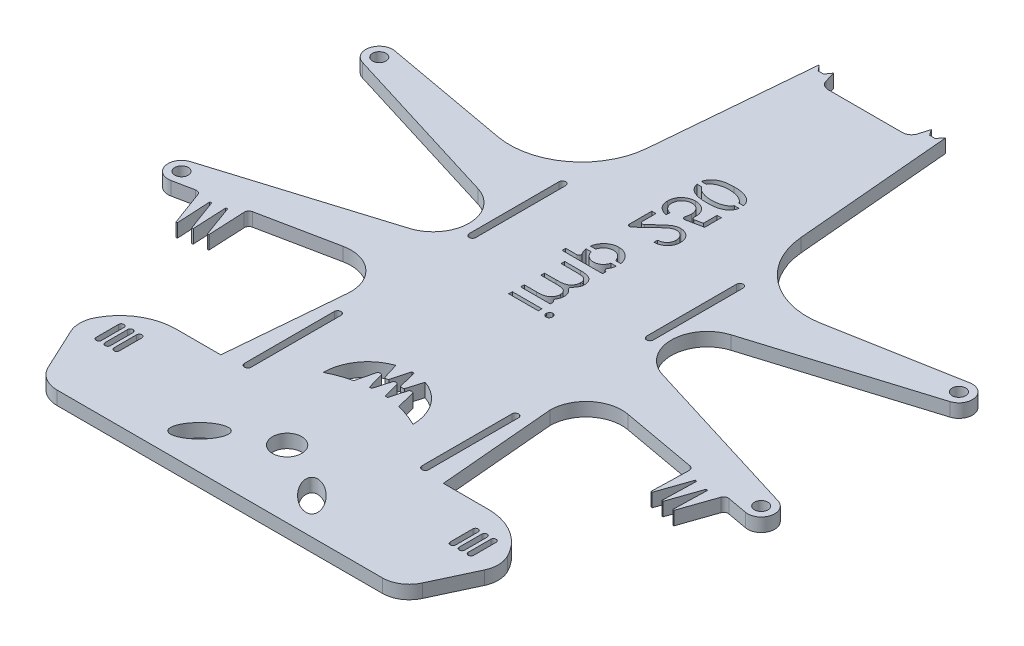
SolidWorks part; units mm, degrees
ref_plane "前视基准面" through (0, 0, 0) normal (0, 0, 1) x (1, 0, 0)
ref_plane "上视基准面" through (0, 0, 0) normal (0, 1, 0) x (1, 0, 0)
ref_plane "右视基准面" through (0, 0, 0) normal (1, 0, 0) x (0, 0, -1)
sketch "草图1" plane through (0, 0, 0) normal (0, 1, 0) x (1, 0, 0)
  line L5 (-65.3843, -19.1333) -> (-28.1418, -7.6445)
  line L6 (-63.9021, -24.9398) -> (-58.5124, -23.8437)
  line L8 (0, 0) -> (0, 91.5573) construction
  line L9 (0, 0) -> (-115.8836, 0) construction
  line L15 (0, 0) -> (0, -124.2991) construction
  line L16 (-15, -65) -> (15, -65) construction
  line L20 (-15.42, -115) -> (17.43, -115) construction
  line L21 (-28, -109.5) -> (-28, -90)
  line L22 (28, -109.5) -> (28, -90)
  line L23 (-17.5, -120) -> (17.5, -120)
  line L28 (22.5, -27) -> (22.5, 27) construction
  line L29 (-22.5, -27) -> (-22.5, 27) construction
  line L30 (28.1418, -7.6445) -> (65.3843, -19.1333)
  line L31 (28.1418, 7.6445) -> (65.3843, 19.1333)
  line L32 (-28, -90) -> (28, -90) construction
  line L33 (28, -90) -> (22.5, -27)
  line L34 (-28, -90) -> (-22.5, -27)
  line L35 (63.9635, -24.9516) -> (58.59, -23.9749)
  line L36 (0, 0) -> (104.501, 0) construction
  line L37 (-28.1418, 7.6445) -> (-65.3843, 19.1333)
  line L39 (22.5, 70) -> (22.5, 27) construction
  line L40 (-22.5, 70) -> (-22.5, 27) construction
  line L41 (31.9307, 19.129) -> (63.9635, 24.9516) construction
  line L42 (-63.9635, 24.9516) -> (-31.9307, 19.129) construction
  line L43 (-17.1562, 34.2114) -> (-14.0779, 69.4717)
  line L44 (63.9635, 24.9516) -> (35.957, 19.8608)
  line L45 (-63.9635, 24.9516) -> (-35.957, 19.8608)
  line L46 (17.1562, 34.2114) -> (14.0779, 69.4717)
  line L47 (51.4721, -37.7563) -> (54.614, -20.4713) construction
  line L48 (43.8592, -31.4611) -> (59.0133, -34.2157) construction
  line L49 (52.3717, -31.9686) -> (52.5699, -24.4476)
  line L50 (52.6668, -32.0223) -> (55.128, -24.9126)
  line L51 (-51.727, -34.6283) -> (-54.8464, -19.2902) construction
  line L52 (-52.1667, -31.7138) -> (-52.5215, -24.1986)
  line L53 (-52.4606, -31.7736) -> (-55.0694, -24.7168)
  line L54 (-55.4614, -24.7965) -> (-55.0688, -32.3041)
  line L55 (-55.3628, -32.3639) -> (-58.5124, -23.8437)
  line L56 (-52.1296, -24.1189) -> (-49.5585, -31.1834)
  line L57 (-49.2645, -31.1236) -> (-49.693, -22.05)
  line L58 (-55.3108, -33.3973) -> (-45.8391, -31.4709) construction
  line L59 (-49.693, -22.05) -> (-32.0641, -18.4647)
  line L60 (49.42, -31.4321) -> (49.6594, -22.3516)
  line L61 (49.7152, -31.4858) -> (52.1764, -24.3761)
  line L62 (55.3233, -32.5052) -> (55.5216, -24.9841)
  line L63 (55.6185, -32.5588) -> (58.59, -23.9749)
  line L64 (49.6594, -22.3516) -> (31.9307, -19.129)
  line L65 (-14.4088, 65.6811) -> (14.4088, 65.6811) construction
  line L70 (-10.8845, 69.4717) -> (-10.1819, 67.1107)
  line L75 (10.8788, 69.4717) -> (10.1832, 67.115)
  line L76 (-8.265, 65.6811) -> (8.265, 65.6811)
  line L77 (-58.5124, -23.8437) -> (-49.693, -22.05) construction
  line L78 (-55.0119, -33.3365) -> (-57.0048, -23.5371) construction
  line L79 (-49.2076, -32.156) -> (-51.2006, -22.3566) construction
  line L80 (-55.3108, -31.8666) -> (-48.2781, -30.4363) construction
  line L81 (-55.5726, -23.2458) -> (-53.8786, -31.5753) construction
  line L82 (-52.6328, -22.6479) -> (-50.9388, -30.9774) construction
  line L83 (-55.174, -25.2057) -> (-50.3177, -24.218) construction
  line L84 (49.6594, -22.3516) -> (58.59, -23.9749) construction
  line L85 (49.3846, -32.4655) -> (51.1731, -22.6267) construction
  line L86 (55.2879, -33.5385) -> (57.0763, -23.6997) construction
  line L87 (49.6529, -30.9897) -> (55.5562, -32.0627) construction
  line L88 (52.6489, -22.895) -> (50.8605, -32.7337) construction
  line L89 (55.6005, -23.4315) -> (53.8121, -33.2703) construction
  line L90 (52.2912, -24.8627) -> (55.2428, -25.3992) construction
  line L95 (-13, 68.1811) -> (-11.8, 68.1811)
  line L96 (13, 68.1811) -> (14.0779, 69.4717)
  line L97 (-13, 68.1811) -> (-14.0779, 69.4717)
  line L98 (-10.8845, 69.4717) -> (-11.8, 68.1811)
  line L99 (10.8788, 69.4717) -> (11.8, 68.1811)
  line L100 (11.8, 68.1811) -> (13, 68.1811)
  circle A0 centre (-64.5, 30) radius 1.5 construction
  circle A1 centre (64.5, 30) radius 1.5 construction
  circle A2 centre (64.5, -30) radius 1.5 construction
  circle A3 centre (-64.5, -30) radius 1.5 construction
  circle A4 centre (-64.5, 30) radius 3 construction
  circle A5 centre (64.5, 30) radius 3 construction
  circle A6 centre (64.5, -30) radius 3 construction
  circle A7 centre (-64.5, -30) radius 3 construction
  circle A10 centre (-64.5, 22) radius 1.5
  circle A11 centre (64.5, 22) radius 1.5
  circle A12 centre (64.5, -22) radius 1.5
  circle A13 centre (-64.5, -22) radius 1.5
  circle A22 centre (0, -90) radius 25
  circle A23 centre (-15, -65) radius 1
  circle A24 centre (15, -65) radius 1
  circle A25 centre (-15.42, -115) radius 1
  circle A26 centre (17.43, -115) radius 1
  arc A27 (-17.5, -120) -> (-28, -109.5) centre (-17.5, -109.5) cw
  arc A28 (17.5, -120) -> (28, -109.5) centre (17.5, -109.5) ccw
  arc A42 (63.9635, -24.9516) -> (65.3843, -19.1333) centre (64.5, -22) ccw
  arc A43 (65.3843, 19.1333) -> (63.9635, 24.9516) centre (64.5, 22) ccw
  arc A44 (28.1418, -7.6445) -> (28.1418, 7.6445) centre (30.5, 0) cw
  arc A46 (22.5, -27) -> (31.9307, -19.129) centre (30.5, -27) cw
  arc A47 (-65.3843, -19.1333) -> (-63.9021, -24.9398) centre (-64.5, -22) ccw
  arc A49 (-28.1418, -7.6445) -> (-28.1418, 7.6445) centre (-30.5, 0) ccw
  arc A50 (-22.5, -27) -> (-32.0641, -18.4647) centre (-30.4697, -26.3042) ccw
  arc A51 (-63.9635, 24.9516) -> (-65.3843, 19.1333) centre (-64.5, 22) ccw
  arc A52 (31.9307, 19.129) -> (22.5, 27) centre (30.5, 27) cw construction
  arc A53 (-31.9307, 19.129) -> (-22.5, 27) centre (-30.5, 27) ccw construction
  arc A54 (-35.957, 19.8608) -> (-17.1562, 34.2114) centre (-33.0955, 35.6029) ccw
  arc A55 (17.1562, 34.2114) -> (35.957, 19.8608) centre (33.0955, 35.6029) ccw
  arc A56 (-8.265, 65.6811) -> (-10.1819, 67.1107) centre (-8.265, 67.6811) cw
  arc A57 (10.1832, 67.115) -> (8.265, 65.6811) centre (8.265, 67.6811) cw
  arc A58 (-55.3628, -32.3639) -> (-55.0688, -32.3041) centre (-55.3108, -31.8666) ccw
  arc A59 (-52.4606, -31.7736) -> (-52.1667, -31.7138) centre (-52.4087, -31.2763) ccw
  arc A60 (-49.5585, -31.1834) -> (-49.2645, -31.1236) centre (-49.5066, -30.6861) ccw
  arc A61 (-55.4614, -24.7965) -> (-55.0694, -24.7168) centre (-55.174, -25.2057) cw
  arc A62 (-52.5215, -24.1986) -> (-52.1296, -24.1189) centre (-52.2342, -24.6078) cw
  arc A63 (49.42, -31.4321) -> (49.7152, -31.4858) centre (49.6529, -30.9897) ccw
  arc A64 (52.3717, -31.9686) -> (52.6668, -32.0223) centre (52.6045, -31.5262) ccw
  arc A65 (55.3233, -32.5052) -> (55.6185, -32.5588) centre (55.5562, -32.0627) ccw
  arc A66 (52.1764, -24.3761) -> (52.5699, -24.4476) centre (52.2912, -24.8627) cw
  arc A67 (55.128, -24.9126) -> (55.5216, -24.9841) centre (55.2428, -25.3992) cw
  point P0 (0, 0)
  point P109 (-9.7565, 65.6811)
  point P112 (9.76, 65.6811)
  dimension "D1" = 3
  dimension "D6" = 6
  dimension "D7" = 6
  dimension "D8" = 6
  dimension "D9" = 6
  dimension "D15" = 3
  dimension "D18" = 6
  dimension "D19" = 16
  dimension "D20" = 8
  dimension "D21" = 22
  dimension "D22" = 50
  dimension "D28" = 2
  dimension "D31" = 2
  dimension "D25" = 45
  dimension "D37" = 27
  dimension "D38" = 16
  dimension "D39" = 10
  dimension "D40" = 6
  dimension "D41" = 6
  dimension "D44" = 8
  dimension "D45" = 8
  dimension "D27" = 22.5
  dimension "D47" = 10.5
  dimension "D48" = 10
  dimension "D17" = 8
  dimension "D12" = 6
  dimension "D13" = 8
  dimension "D16" = 8
  dimension "D60" = 2
  dimension "D61" = 2
  dimension "D62" = 0.5
  dimension "D67" = 0.5
  dimension "D70" = 0.5
  dimension "D74" = 0.5
  dimension "D77" = 0.5
  dimension "D81" = 0.5
  dimension "D66" = 0.5
  dimension "D86" = 0.5
  dimension "D90" = 0.5
  dimension "D93" = 0.5
  dimension "D2" = 129
  dimension "D3" = 60
  dimension "D4" = 30
  dimension "D5" = 64.5
  dimension "D10" = 27
  dimension "D11" = 27
  dimension "D14" = 9.7565
  dimension "D23" = 30
  dimension "D24" = 15
  dimension "D26" = 30
  dimension "D29" = 32.85
  dimension "D30" = 2.43
  dimension "D32" = 27
  dimension "D33" = 28
  dimension "D34" = 28
  dimension "D35" = 35
  dimension "D36" = 17.5
  dimension "D42" = 45
  dimension "D43" = 22.5
  dimension "D46" = 120
  dimension "D49" = 10
  dimension "D50" = 3
  dimension "D51" = 3
  dimension "D52" = 3
  dimension "D53" = 1.5
  dimension "D54" = 10
  dimension "D55" = 3
  dimension "D56" = 1.5
  dimension "D57" = 65.6811
  dimension "D58" = 10.1819
  dimension "D59" = 10.1832
  dimension "D63" = 1.5
  dimension "D64" = 0.15
  dimension "D65" = 0.15
  dimension "D68" = 0.15
  dimension "D69" = 0.15
  dimension "D71" = 0.15
  dimension "D72" = 0.15
  dimension "D73" = 2
  dimension "D75" = 0.2
  dimension "D76" = 0.2
  dimension "D78" = 0.2
  dimension "D79" = 0.2
  dimension "D80" = 1.5
  dimension "D82" = 0.15
  dimension "D83" = 0.15
  dimension "D84" = 0.15
  dimension "D85" = 0.15
  dimension "D87" = 0.15
  dimension "D88" = 0.15
  dimension "D89" = 2
  dimension "D91" = 0.2
  dimension "D92" = 0.2
  dimension "D94" = 0.2
  dimension "D95" = 0.2
  dimension "D96" = 3.7906
  dimension "D97" = 8.265
  dimension "D98" = 3.7906
  dimension "D99" = 8.265
  dimension "D100" = 9.76
  dimension "D101" = 22.5
  dimension "D102" = 26
  dimension "D103" = 13
  dimension "D104" = 2.5
  dimension "D105" = 10.8845
  dimension "D106" = 10.8788
  dimension "D107" = 1.2
  dimension "D108" = 1.2
extrude "凸台-拉伸1" add sketch "草图1" along normal blind 3
sketch "草图2" plane through (0, 0, 0) normal (0, -1, 0) x (1, 0, 0)
  line L0 (0, 133.3282) -> (0, -97.043) construction
  line L1 (-19.75, 2) -> (-19.75, -18) construction
  line L2 (-19, 2) -> (-19, -18)
  line L3 (-20.5, 2) -> (-20.5, -18)
  line L4 (19.75, 2) -> (19.75, -18) construction
  line L5 (20.5, 2) -> (20.5, -18)
  line L6 (19, 2) -> (19, -18)
  line L7 (0, 0) -> (56.7659, 0) construction
  line L8 (-19.75, 52) -> (-19.75, 32) construction
  line L9 (-19, 52) -> (-19, 32)
  line L10 (-20.5, 52) -> (-20.5, 32)
  line L11 (19.75, 52) -> (19.75, 32) construction
  line L12 (20.5, 52) -> (20.5, 32)
  line L13 (19, 52) -> (19, 32)
  arc A0 (-19, 2) -> (-20.5, 2) centre (-19.75, 2) ccw
  arc A1 (-20.5, -18) -> (-19, -18) centre (-19.75, -18) ccw
  arc A2 (20.5, 2) -> (19, 2) centre (19.75, 2) ccw
  arc A3 (19, -18) -> (20.5, -18) centre (19.75, -18) ccw
  arc A4 (-19, 52) -> (-20.5, 52) centre (-19.75, 52) ccw
  arc A5 (-20.5, 32) -> (-19, 32) centre (-19.75, 32) ccw
  arc A6 (20.5, 52) -> (19, 52) centre (19.75, 52) ccw
  arc A7 (19, 32) -> (20.5, 32) centre (19.75, 32) ccw
  arc A8 (-10, 45) -> (10, 45) centre (0, 45) ccw
  arc A9 (-10, 45) -> (10, 45) centre (0, 64.5959) ccw
  point P5 (-19.75, -8)
  point P10 (19.75, -8)
  point P19 (-19.75, 42)
  point P26 (19.75, 42)
  dimension "D6" = 42
  dimension "D8" = 10
  dimension "D9" = 22
  dimension "D1" = 1.5
  dimension "D2" = 20
  dimension "D3" = 19
  dimension "D4" = 19
  dimension "D5" = 8
  dimension "D7" = 45
  dimension "D10" = 10
extrude "切除-拉伸1" cut sketch "草图2" against normal blind 3
sketch "草图3" plane through (0, 0, 0) normal (0, -1, 0) x (1, 0, 0)
  line L0 (0, 67.5428) -> (0, 43.0807) construction
  line L1 (-3.5, 60.2388) -> (-3.5, 43.3854) construction
  line L2 (3.5, 60.0167) -> (3.5, 43.3854) construction
  line L3 (-1.5, 42.6471) -> (-0.4454, 38.96)
  line L4 (0.4454, 38.96) -> (1.5, 42.6471)
  line L5 (-5.2946, 37.5) -> (4.5072, 37.5) construction
  line L6 (-3.0546, 38.96) -> (-2, 42.687)
  line L7 (-5, 43.1716) -> (-3.9454, 38.96)
  line L8 (3.0546, 38.96) -> (2, 42.687)
  line L9 (3.9454, 38.96) -> (5, 43.1716)
  line L10 (-5.8174, 40.5) -> (6.3675, 40.5) construction
  line L11 (-5.8021, 35) -> (6.2608, 35) construction
  line L12 (-1.75, 52.0659) -> (-1.75, 44.2103) construction
  line L13 (1.75, 52.0659) -> (1.75, 33.5429) construction
  line L14 (-1.3046, 39.04) -> (-0.25, 35.0031)
  line L15 (-2.1906, 39.0439) -> (-3.25, 35.5429)
  line L16 (1.3046, 39.04) -> (0.25, 35.0031)
  line L17 (2.1954, 39.04) -> (3.25, 35.5429)
  line L18 (-5, 43.1716) -> (-5, 44.1716)
  line L19 (-5, 44.1716) -> (5, 44.1716)
  line L20 (5, 44.1716) -> (5, 43.1716)
  line L21 (-2, 42.687) -> (-2, 43.687)
  line L22 (-2, 43.687) -> (-1.5, 43.687)
  line L23 (-1.5, 43.687) -> (-1.5, 42.6471)
  line L24 (1.5, 42.6471) -> (1.5, 43.687)
  line L25 (1.5, 43.687) -> (2, 43.687)
  line L26 (2, 43.687) -> (2, 42.687)
  line L27 (-3.25, 35.5429) -> (-3.25, 33.5429)
  line L28 (-3.25, 33.5429) -> (3.25, 33.5429)
  line L29 (3.25, 33.5429) -> (3.25, 35.5429)
  line L30 (-0.25, 35.0031) -> (-0.25, 34.0031)
  line L31 (-0.25, 34.0031) -> (0.25, 34.0031)
  line L32 (0.25, 34.0031) -> (0.25, 35.0031)
  arc A0 (-10, 45) -> (10, 45) centre (0, 64.5959) ccw construction
  arc A1 (-10, 45) -> (10, 45) centre (0, 64.5959) ccw construction
  arc A2 (-10, 45) -> (10, 45) centre (0, 45) ccw construction
  arc A3 (-10, 45) -> (10, 45) centre (0, 45) ccw construction
  arc A4 (-3.9454, 38.96) -> (-3.0546, 38.96) centre (-3.5, 39.5) ccw
  arc A5 (0.4454, 38.96) -> (-0.4454, 38.96) centre (0, 39.5) cw
  arc A6 (3.9454, 38.96) -> (3.0546, 38.96) centre (3.5, 39.5) cw
  arc A7 (-2.1906, 39.0439) -> (-1.3046, 39.04) centre (-1.75, 38.5) cw
  arc A8 (1.3046, 39.04) -> (2.1954, 39.04) centre (1.75, 38.5) cw
  dimension "D21" = 0.7
  dimension "D25" = 0.7
  dimension "D26" = 0.7
  dimension "D28" = 0.7
  dimension "D33" = 0.7
  dimension "D1" = 3.5
  dimension "D2" = 3.5
  dimension "D3" = 7.5
  dimension "D4" = 3
  dimension "D5" = 1.5
  dimension "D6" = 1.5
  dimension "D7" = 1.5
  dimension "D8" = 3
  dimension "D9" = 1.5
  dimension "D10" = 5.5
  dimension "D11" = 1.75
  dimension "D12" = 3.5
  dimension "D13" = 1.5
  dimension "D14" = 1.5
  dimension "D15" = 1.5
  dimension "D16" = 1.5
  dimension "D17" = 1
  dimension "D18" = 1
  dimension "D19" = 1
  dimension "D20" = 2
  dimension "D22" = 2
  dimension "D23" = 1.46
  dimension "D24" = 1.46
  dimension "D27" = 2
  dimension "D29" = 1.4561
  dimension "D30" = 1.46
  dimension "D31" = 2
  dimension "D32" = 1.46
  dimension "D34" = 1.46
extrude "凸台-拉伸2" add sketch "草图3" against normal blind 3
sketch "草图4" plane through (0, 0, 0) normal (0, -1, 0) x (1, 0, 0)
  line L0 (0, 0) -> (0, 140.5969) construction
  line L1 (-28, 108) -> (-21.4476, 108)
  line L2 (-17.5, 120) -> (17.5, 120) construction
  line L3 (-28, 90) -> (28, 90) construction
  line L4 (-28, 90) -> (-28, 109.5) construction
  line L5 (28, 109.5) -> (28, 90) construction
  line L6 (-21.4476, 113) -> (-21.4476, 119.2297)
  line L7 (21.4476, 119.2297) -> (21.4476, 113)
  line L8 (21.4476, 108) -> (28, 108)
  line L9 (-21.4476, 113) -> (-27.3995, 113)
  line L10 (21.4476, 113) -> (27.3995, 113)
  line L11 (-28, 108) -> (-28, 90)
  line L12 (28, 108) -> (28, 90)
  circle A0 centre (0, 90) radius 25 construction
  circle A1 centre (0, 90) radius 25 construction
  arc A2 (-21.4476, 108) -> (-28, 90) centre (0, 90) ccw
  arc A3 (28, 90) -> (21.4476, 108) centre (0, 90) ccw
  arc A4 (-17.5, 120) -> (-28, 109.5) centre (-17.5, 109.5) ccw construction
  arc A5 (28, 109.5) -> (17.5, 120) centre (17.5, 109.5) ccw construction
  arc A6 (-21.4476, 119.2297) -> (-27.3995, 113) centre (-17.5, 109.5) ccw
  arc A7 (27.3995, 113) -> (21.4476, 119.2297) centre (17.5, 109.5) ccw
  dimension "D1" = 12
  dimension "D4" = 5
  dimension "D5" = 5
extrude "切除-拉伸2" cut sketch "草图4" against normal blind 3
sketch "草图6" plane through (0, 0, 0) normal (0, -1, 0) x (1, 0, 0)
  line L0 (-21.4476, 119.2297) -> (-21.4476, 139)
  line L1 (-18.4476, 142) -> (18.4476, 142)
  line L2 (21.4476, 139) -> (21.4476, 119.2297)
  line L3 (-17.5, 120) -> (17.5, 120) construction
  line L4 (0, 0) -> (0, 166.5632) construction
  line L5 (-21.4476, 131) -> (21.4476, 131) construction
  line L6 (-21.4476, 139) -> (-18.4476, 142)
  line L7 (18.4476, 142) -> (21.4476, 139)
  line L8 (-21.4476, 119.2297) -> (21.4476, 119.2297)
  circle A0 centre (0, 131) radius 3
  point P1 (-21.4476, 142)
  point P4 (21.4476, 142)
  dimension "D3" = 6
  dimension "D1" = 22
  dimension "D2" = 11
extrude "凸台-拉伸3" add sketch "草图6" against normal blind 3
sketch "草图7" plane through (0, 0, 0) normal (0, -1, 0) x (1, 0, 0)
  line L0 (-21.4476, 108) -> (-28, 108) construction
  line L1 (-21.4476, 108) -> (-28, 108) construction
  line L2 (28, 108) -> (21.4476, 108) construction
  line L3 (28, 108) -> (21.4476, 108) construction
  line L4 (-22.5, 27) -> (-28, 90) construction
  line L5 (-26.6119, 74.1001) -> (-28, 90)
  line L6 (28, 90) -> (22.5, 27) construction
  line L7 (28, 90) -> (26.6119, 74.1001)
  line L8 (-25.2389, 108) -> (-21.4476, 108)
  line L9 (21.4476, 108) -> (25.2389, 108)
  circle A0 centre (0, 90) radius 25 construction
  circle A1 centre (0, 90) radius 25 construction
  arc A2 (-25.2389, 108) -> (-26.6119, 74.1001) centre (0, 90) ccw
  arc A3 (26.6119, 74.1001) -> (25.2389, 108) centre (0, 90) ccw
  arc A4 (-21.4476, 108) -> (-28, 90) centre (0, 90) ccw construction
  arc A5 (-21.4476, 108) -> (-28, 90) centre (0, 90) ccw
  arc A6 (28, 90) -> (21.4476, 108) centre (0, 90) ccw construction
  arc A7 (28, 90) -> (21.4476, 108) centre (0, 90) ccw
  dimension "D1" = 62
extrude "凸台-拉伸4" add sketch "草图7" against normal blind 3
sketch "草图8" plane through (0, 0, 0) normal (0, -1, 0) x (1, 0, 0)
  line L0 (-22.5, 27) -> (-26.6119, 74.1001) construction
  line L1 (-25.6429, 63) -> (-26.6119, 74.1001)
  line L2 (26.6119, 74.1001) -> (22.5, 27) construction
  line L3 (26.6119, 74.1001) -> (25.6429, 63)
  line L4 (-25.6429, 63) -> (25.6429, 63)
  line L5 (-25.2389, 108) -> (-28, 108) construction
  line L6 (-25.2389, 108) -> (-28, 108)
  line L7 (-28, 108) -> (-28, 109.5) construction
  line L8 (-28, 108) -> (-28, 109.5)
  line L9 (28, 108) -> (25.2389, 108) construction
  line L10 (28, 109.5) -> (28, 108) construction
  line L11 (21.4476, 113) -> (27.3995, 113) construction
  line L12 (21.4476, 139) -> (21.4476, 113) construction
  line L13 (21.4476, 139) -> (18.4476, 142) construction
  line L14 (18.4476, 142) -> (-18.4476, 142) construction
  line L15 (-18.4476, 142) -> (-21.4476, 139) construction
  line L16 (-21.4476, 113) -> (-21.4476, 139) construction
  line L17 (-27.3995, 113) -> (-21.4476, 113) construction
  line L18 (28, 108) -> (25.2389, 108)
  line L19 (28, 109.5) -> (28, 108)
  line L20 (21.4476, 113) -> (27.3995, 113)
  line L21 (21.4476, 139) -> (21.4476, 113)
  line L22 (21.4476, 139) -> (18.4476, 142)
  line L23 (18.4476, 142) -> (-18.4476, 142)
  line L24 (-18.4476, 142) -> (-21.4476, 139)
  line L25 (-21.4476, 113) -> (-21.4476, 139)
  line L26 (-27.3995, 113) -> (-21.4476, 113)
  circle A1 centre (0, 63) radius 3.25 construction
  arc A2 (-25.2389, 108) -> (-26.6119, 74.1001) centre (0, 90) ccw construction
  arc A3 (-25.2389, 108) -> (-26.6119, 74.1001) centre (0, 90) ccw
  arc A4 (-27.3995, 113) -> (-28, 109.5) centre (-17.5, 109.5) ccw construction
  arc A5 (-27.3995, 113) -> (-28, 109.5) centre (-17.5, 109.5) ccw
  arc A6 (26.6119, 74.1001) -> (25.2389, 108) centre (0, 90) ccw construction
  arc A7 (28, 109.5) -> (27.3995, 113) centre (17.5, 109.5) ccw construction
  arc A8 (26.6119, 74.1001) -> (25.2389, 108) centre (0, 90) ccw
  arc A9 (28, 109.5) -> (27.3995, 113) centre (17.5, 109.5) ccw
  dimension "D1" = 6.5
  dimension "D2" = 63
extrude "切除-拉伸3" cut sketch "草图8" against normal blind 10
sketch "草图10" plane through (0, 0, 0) normal (0, -1, 0) x (1, 0, 0)
  line L0 (-25.6429, 63) -> (25.6429, 63) construction
  line L1 (-46.9976, 63) -> (47.0024, 63) construction
  line L2 (-36.1783, 78) -> (36.1794, 78)
  line L3 (0, 63) -> (0, 109.6816) construction
  line L4 (-34.7501, 53) -> (34.755, 53)
  line L5 (-41.6157, 74.5366) -> (-46.0027, 65.1325)
  line L6 (41.6161, 74.538) -> (46.0066, 65.1333)
  circle A0 centre (0, 63) radius 3.25
  arc A1 (-45.9332, 59.9152) -> (-34.7501, 53) centre (-34.7501, 65.5) ccw
  arc A2 (45.9374, 59.9139) -> (34.755, 53) centre (34.755, 65.5) cw
  arc A3 (-41.6157, 74.5366) -> (-36.1783, 78) centre (-36.1783, 72) cw
  arc A4 (41.6161, 74.538) -> (36.1794, 78) centre (36.1794, 72) ccw
  arc A5 (-45.9332, 59.9152) -> (-46.0027, 65.1325) centre (-40.5653, 62.5959) cw
  arc A6 (45.9374, 59.9139) -> (46.0066, 65.1333) centre (40.5698, 62.5952) ccw
  point P13 (0, 0)
  point P18 (-40, 78)
  point P21 (40, 78)
  point P27 (47.0024, 63)
  dimension "D1" = 6.5
  dimension "D8" = 6
  dimension "D3" = 34.755
  dimension "D9" = 6
  dimension "D10" = 6
  dimension "D11" = 6
  dimension "D2" = 94
  dimension "D4" = 15
  dimension "D5" = 80
  dimension "D6" = 40
  dimension "D7" = 10
  dimension "D12" = 34.7501
extrude "凸台-拉伸5" add sketch "草图10" against normal blind 3
sketch "草图12" plane through (0, 0, 0) normal (0, -1, 0) x (1, 0, 0)
  line L0 (0, 0) -> (0, 80.2882) construction
  line L1 (-24.7698, 53) -> (24.7698, 53) construction
  line L2 (-12.5, 53) -> (-12.5, 78) construction
  line L3 (36.1794, 78) -> (-36.1783, 78) construction
  line L4 (12.5, 53) -> (12.5, 78) construction
  line L5 (-46.412, 70) -> (46.4169, 70) construction
  line L6 (-16.0355, 73.5355) -> (-8.9645, 66.4645) construction
  line L7 (-14.091, 68.409) -> (-10.909, 71.591) construction
  line L8 (-41.412, 63.5) -> (-41.412, 58.5) construction
  line L9 (-40.812, 63.5) -> (-40.812, 58.5)
  line L10 (-42.012, 63.5) -> (-42.012, 58.5)
  line L11 (-46.412, 61) -> (46.4169, 61) construction
  line L12 (-39.412, 63.5) -> (-39.412, 58.5) construction
  line L13 (-38.812, 63.5) -> (-38.812, 58.5)
  line L14 (-40.012, 63.5) -> (-40.012, 58.5)
  line L15 (-37.412, 63.5) -> (-37.412, 58.5) construction
  line L16 (-36.812, 63.5) -> (-36.812, 58.5)
  line L17 (-38.012, 63.5) -> (-38.012, 58.5)
  line L18 (37.412, 63.5) -> (37.412, 58.5) construction
  line L19 (36.812, 63.5) -> (36.812, 58.5)
  line L20 (38.012, 63.5) -> (38.012, 58.5)
  line L21 (39.412, 63.5) -> (39.412, 58.5) construction
  line L22 (38.812, 63.5) -> (38.812, 58.5)
  line L23 (40.012, 63.5) -> (40.012, 58.5)
  line L24 (41.412, 63.5) -> (41.412, 58.5) construction
  line L25 (40.812, 63.5) -> (40.812, 58.5)
  line L26 (42.012, 63.5) -> (42.012, 58.5)
  arc A0 (3.25, 63) -> (-3.25, 63) centre (0, 63) ccw construction
  arc A1 (3.25, 63) -> (-3.25, 63) centre (0, 63) ccw construction
  circle A2 centre (0, 63) radius 3.25
  arc A4 (-45.9332, 59.9152) -> (-34.7501, 53) centre (-34.7501, 65.5) ccw construction
  arc A5 (34.755, 53) -> (45.9374, 59.9139) centre (34.755, 65.5) ccw construction
  arc A6 (34.755, 53) -> (45.9374, 59.9139) centre (34.755, 65.5) ccw construction
  arc A7 (-40.812, 63.5) -> (-42.012, 63.5) centre (-41.412, 63.5) ccw
  arc A8 (-42.012, 58.5) -> (-40.812, 58.5) centre (-41.412, 58.5) ccw
  arc A10 (-45.9332, 59.9152) -> (-34.7501, 53) centre (-34.7501, 65.5) ccw construction
  arc A11 (-38.812, 63.5) -> (-40.012, 63.5) centre (-39.412, 63.5) ccw
  arc A12 (-40.012, 58.5) -> (-38.812, 58.5) centre (-39.412, 58.5) ccw
  arc A13 (-36.812, 63.5) -> (-38.012, 63.5) centre (-37.412, 63.5) ccw
  arc A14 (-38.012, 58.5) -> (-36.812, 58.5) centre (-37.412, 58.5) ccw
  arc A15 (36.812, 63.5) -> (38.012, 63.5) centre (37.412, 63.5) cw
  arc A16 (38.012, 58.5) -> (36.812, 58.5) centre (37.412, 58.5) cw
  arc A17 (38.812, 63.5) -> (40.012, 63.5) centre (39.412, 63.5) cw
  arc A18 (40.012, 58.5) -> (38.812, 58.5) centre (39.412, 58.5) cw
  arc A19 (40.812, 63.5) -> (42.012, 63.5) centre (41.412, 63.5) cw
  arc A20 (42.012, 58.5) -> (40.812, 58.5) centre (41.412, 58.5) cw
  ellipse E0 centre (-12.5, 70) end of major axis (-8.9645, 66.4645) minor radius 2.25
  ellipse E1 centre (12.5, 70) end of major axis (8.9645, 66.4645) minor radius 2.25
  point P43 (-41.412, 61)
  point P52 (-39.412, 61)
  point P65 (-37.412, 61)
  point P72 (37.412, 61)
  point P79 (39.412, 61)
  point P86 (41.412, 61)
  dimension "D1" = 24.7698
  dimension "D2" = 12.5
  dimension "D3" = 12.5
  dimension "D4" = 8
  dimension "D5" = 45
  dimension "D6" = 10
  dimension "D7" = 4.5
  dimension "D8" = 8
  dimension "D9" = 1.2
  dimension "D10" = 5
  dimension "D11" = 5
  dimension "D13" = 2
  dimension "D12" = 3
extrude "切除-拉伸4" cut sketch "草图12" against normal blind 3
sketch "草图13" plane through (0, 0, 0) normal (0, -1, 0) x (1, 0, 0)
  line L0 (-4.5, 10) -> (-4.5, -61.1131) construction
  text T0 "imp 250" font "Century Gothic" height 9
  point P0 (-3.4311, 9.1803)
  point P4 (0, -61.9328)
  point P5 (0, 0)
  dimension "D1" = 10
  dimension "D2" = 4.5
extrude "切除-拉伸6" cut sketch "草图13" against normal blind 3
sketch "草图14" plane through (0, 0, 0) normal (0, -1, 0) x (1, 0, 0)
  line L0 (-4.6154, -8.6058) -> (2.1923, -8.5805) construction
  line L1 (-1.1935, -12.0385) -> (-1.1935, -6.2358) construction
  line L2 (0.9803, -8.085) -> (2.4825, -8.085)
  line L3 (0.984, -9.085) -> (2.4825, -9.085)
  line L4 (2.4825, -8.085) -> (2.4825, -9.085)
  line L5 (-4.8695, -8.085) -> (-4.8695, -9.085)
  line L6 (-3.4071, -9.085) -> (-4.8695, -9.085)
  line L7 (-3.4034, -8.085) -> (-4.8695, -8.085)
  line L8 (-0.0036, -30.3846) -> (-0.0036, -36.5) construction
  line L9 (-4.7308, -33.3936) -> (4.7308, -33.3936) construction
  line L10 (3.6134, -32.8936) -> (5.1969, -32.8936)
  line L11 (3.6134, -33.8936) -> (5.1969, -33.8936)
  line L12 (5.1969, -32.8936) -> (5.1969, -33.8936)
  line L13 (-5.2041, -32.8936) -> (-5.2041, -33.8936)
  line L14 (-3.6134, -33.8936) -> (-5.2041, -33.8936)
  line L15 (-3.6134, -32.8936) -> (-5.2041, -32.8936)
  arc A0 (-3.4071, -9.085) -> (0.984, -9.085) centre (-1.2115, -8.5931) ccw
  arc A1 (0.9803, -8.085) -> (-3.4034, -8.085) centre (-1.2115, -8.5931) ccw
  ellipse E0 centre (0, -33.3936) end of major axis (3.7308, -33.3936) minor radius 2.009 (-3.6134, -33.8936) -> (3.6134, -33.8936) ccw
  ellipse E1 centre (0, -33.3936) end of major axis (3.7308, -33.3936) minor radius 2.009 (3.6134, -32.8936) -> (-3.6134, -32.8936) ccw
  spline S0 degree 3 poles (1999.1139, -116.8053) (-26.3066, 9.3137) (3.2455, -0.9377) (2.1371, -9.2675) (2.0596, -9.5946) (1.948, -9.9072) (1.81, -10.2087) (1.6359, -10.4947) (1.4343, -10.7696) (1.2023, -11.0266) (0.9512, -11.264) (0.6812, -11.4693) (0.401, -11.6464) (0.1063, -11.7895) (-0.2005, -11.9017) (-0.5207, -11.9814) (-8.481, -13.118) (-18.5333, 17.21) (115.3668, -2008.5336) knots -4.485893 -4.485893 -4.485893 -4.485893 0.065081 0.128636 0.190653 0.252125 0.313446 0.375227 0.438498 0.503285 0.56801 0.630879 0.692154 0.752552 0.813191 0.873985 0.936258 5.28658 5.28658 5.28658 5.28658 only from (2.1923, -8.5805) to (-1.1935, -12.0385) construction
  spline S1 degree 3 poles (-126.1181, -2007.9855) (16.4205, 17.6121) (6.1423, -13.1304) (-1.8785, -11.9807) (-2.2043, -11.9045) (-2.5148, -11.7904) (-2.8145, -11.6506) (-3.0983, -11.4758) (-3.3689, -11.2706) (-3.6218, -11.0358) (-3.8548, -10.7811) (-4.0584, -10.5088) (-4.2302, -10.2229) (-4.3717, -9.9248) (-4.4807, -9.6135) (-4.5579, -9.2891) (-5.7016, -1.2502) (24.8151, 8.9334) (-2000.9105, -127.4921) knots -4.309051 -4.309051 -4.309051 -4.309051 0.064924 0.12804 0.189582 0.250704 0.311716 0.373236 0.435751 0.500337 0.564943 0.627525 0.689157 0.750169 0.810752 0.872294 0.93541 5.317858 5.317858 5.317858 5.317858 only from (-1.1935, -12.0385) to (-4.6154, -8.6058) construction
  spline S2 degree 3 poles (2.1923, -8.5805) (2.1889, -8.6973) (2.1823, -8.928) (2.1371, -9.2675) (2.0596, -9.5946) (1.948, -9.9072) (1.81, -10.2087) (1.6359, -10.4947) (1.4343, -10.7696) (1.2023, -11.0266) (0.9512, -11.264) (0.6812, -11.4693) (0.401, -11.6464) (0.1063, -11.7895) (-0.2005, -11.9017) (-0.5207, -11.9814) (-0.8531, -12.0289) (-1.0792, -12.0352) (-1.1935, -12.0385) knots 0 0 0 0 0.065081 0.128636 0.190653 0.252125 0.313446 0.375227 0.438498 0.503285 0.56801 0.630879 0.692154 0.752552 0.813191 0.873985 0.936258 1 1 1 1 construction
  spline S3 degree 3 poles (-1.1935, -12.0385) (-1.3103, -12.0353) (-1.5405, -12.0291) (-1.8785, -11.9807) (-2.2043, -11.9045) (-2.5148, -11.7904) (-2.8145, -11.6506) (-3.0983, -11.4758) (-3.3689, -11.2706) (-3.6218, -11.0358) (-3.8548, -10.7811) (-4.0584, -10.5088) (-4.2302, -10.2229) (-4.3717, -9.9248) (-4.4807, -9.6135) (-4.5579, -9.2891) (-4.6059, -8.9516) (-4.6122, -8.7219) (-4.6154, -8.6058) knots 0 0 0 0 0.064924 0.12804 0.189582 0.250704 0.311716 0.373236 0.435751 0.500337 0.564943 0.627525 0.689157 0.750169 0.810752 0.872294 0.93541 1 1 1 1 construction
  spline S4 degree 3 poles (2002.5902, -124.144) (-19.0241, -20.2285) (5.4033, -27.672) (4.703, -33.818) (4.6633, -34.0236) (4.6069, -34.2234) (4.537, -34.4192) (4.4493, -34.6093) (4.3473, -34.795) (4.2274, -34.9733) (4.0937, -35.1461) (3.9426, -35.3092) (3.7756, -35.4627) (3.5945, -35.6085) (3.3957, -35.7423) (3.1829, -35.8698) (2.9521, -35.9839) (2.7074, -36.0938) (2.4418, -36.1886) (2.157, -36.2742) (1.8495, -36.3433) (1.521, -36.4009) (1.1703, -36.4455) (0.798, -36.478) (-12.9041, -37.0747) (-26.9071, -16.0629) (-0.5618, -2036.3224) knots -2.816592 -2.816592 -2.816592 -2.816592 0.033788 0.067194 0.099862 0.132567 0.165151 0.197913 0.231319 0.265083 0.299255 0.334399 0.369943 0.406284 0.444064 0.482998 0.523354 0.565537 0.609613 0.656391 0.705885 0.758325 0.813832 0.872795 0.934722 7.288273 7.288273 7.288273 7.288273 only from (4.7308, -33.3936) to (-0.0036, -36.5) construction
  spline S5 degree 3 poles (6.5367, -2036.3371) (26.9533, -16.2497) (12.9581, -37.0706) (-0.8016, -36.4782) (-1.1719, -36.4447) (-1.5212, -36.4034) (-1.8475, -36.3445) (-2.1539, -36.2776) (-2.4377, -36.1944) (-2.7018, -36.1008) (-2.9454, -35.9933) (-3.1741, -35.8782) (-3.3868, -35.7515) (-3.5856, -35.6169) (-3.7683, -35.4724) (-3.9354, -35.3182) (-4.0869, -35.1543) (-4.2224, -34.9811) (-4.3408, -34.8) (-4.4468, -34.615) (-4.5327, -34.4223) (-4.6053, -34.2261) (-4.6618, -34.0248) (-4.7005, -33.8184) (-5.4503, -28.0104) (20.461, -20.5648) (-2001.5481, -144.3408) knots -6.321684 -6.321684 -6.321684 -6.321684 0.065054 0.126756 0.185491 0.240732 0.29294 0.342141 0.388882 0.432636 0.474483 0.514623 0.553594 0.591409 0.628006 0.663583 0.698759 0.733361 0.767394 0.800969 0.83402 0.866999 0.899733 0.932711 0.96618 3.66314 3.66314 3.66314 3.66314 only from (-0.0036, -36.5) to (-4.7308, -33.3936) construction
  spline S6 degree 3 poles (2.6367, 1969.4415) (-25.8736, -52.8133) (-12.3449, -29.8172) (0.8292, -30.4053) (1.2122, -30.4356) (1.57, -30.4771) (1.9026, -30.5276) (2.2092, -30.595) (2.4912, -30.6717) (2.7495, -30.7605) (2.9876, -30.8608) (3.2098, -30.9699) (3.4159, -31.0922) (3.609, -31.2208) (3.7869, -31.3605) (3.9493, -31.5098) (4.0963, -31.6702) (4.2297, -31.8385) (4.3458, -32.0157) (4.4505, -32.1965) (4.5364, -32.3839) (4.607, -32.5764) (4.6635, -32.7732) (4.7027, -32.9753) (5.4116, -38.9649) (-19.4509, -46.3587) (2002.2715, 64.2043) knots -6.075624 -6.075624 -6.075624 -6.075624 0.068599 0.133255 0.194325 0.251295 0.304533 0.354258 0.400506 0.443439 0.484046 0.523286 0.561079 0.597939 0.633559 0.668551 0.702734 0.736926 0.770536 0.803434 0.836171 0.868452 0.90084 0.933462 0.966255 3.764854 3.764854 3.764854 3.764854 only from (-0.0036, -30.3846) to (4.7308, -33.3936) construction
  spline S7 degree 3 poles (-2002.4555, 60.4569) (19.3725, -46.3462) (-5.4092, -38.9846) (-4.7028, -32.9753) (-4.6631, -32.7735) (-4.6091, -32.577) (-4.5404, -32.3853) (-4.4532, -32.2003) (-4.3519, -32.0196) (-4.2368, -31.844) (-4.1048, -31.6768) (-3.9588, -31.5171) (-3.7952, -31.3689) (-3.6166, -31.231) (-3.4244, -31.1001) (-3.2169, -30.979) (-2.9926, -30.8701) (-2.7532, -30.7676) (-2.493, -30.6772) (-2.2095, -30.598) (-1.9012, -30.532) (-1.5689, -30.4789) (-1.2123, -30.4351) (-0.8309, -30.4055) (12.2073, -29.8149) (25.6301, -52.8613) (-5.415, 1969.409) knots -2.777404 -2.777404 -2.777404 -2.777404 0.033789 0.066626 0.099291 0.131645 0.163602 0.196122 0.228923 0.262181 0.296016 0.330245 0.365089 0.400982 0.437654 0.475743 0.515291 0.556327 0.599681 0.646343 0.696413 0.749766 0.806562 0.867427 0.931883 7.020425 7.020425 7.020425 7.020425 only from (-4.7308, -33.3936) to (-0.0036, -30.3846) construction
  spline S8 degree 3 poles (4.7308, -33.3936) (4.7295, -33.4652) (4.727, -33.6076) (4.703, -33.818) (4.6633, -34.0236) (4.6069, -34.2234) (4.537, -34.4192) (4.4493, -34.6093) (4.3473, -34.795) (4.2274, -34.9733) (4.0937, -35.1461) (3.9426, -35.3092) (3.7756, -35.4627) (3.5945, -35.6085) (3.3957, -35.7423) (3.1829, -35.8698) (2.9521, -35.9839) (2.7074, -36.0938) (2.4418, -36.1886) (2.157, -36.2742) (1.8495, -36.3433) (1.521, -36.4009) (1.1703, -36.4455) (0.798, -36.478) (0.404, -36.4951) (0.1346, -36.4983) (-0.0036, -36.5) knots 0 0 0 0 0.033788 0.067194 0.099862 0.132567 0.165151 0.197913 0.231319 0.265083 0.299255 0.334399 0.369943 0.406284 0.444064 0.482998 0.523354 0.565537 0.609613 0.656391 0.705885 0.758325 0.813832 0.872795 0.934722 1 1 1 1 construction
  spline S9 degree 3 poles (-0.0036, -36.5) (-0.1412, -36.4983) (-0.4094, -36.4951) (-0.8016, -36.4782) (-1.1719, -36.4447) (-1.5212, -36.4034) (-1.8475, -36.3445) (-2.1539, -36.2776) (-2.4377, -36.1944) (-2.7018, -36.1008) (-2.9454, -35.9933) (-3.1741, -35.8782) (-3.3868, -35.7515) (-3.5856, -35.6169) (-3.7683, -35.4724) (-3.9354, -35.3182) (-4.0869, -35.1543) (-4.2224, -34.9811) (-4.3408, -34.8) (-4.4468, -34.615) (-4.5327, -34.4223) (-4.6053, -34.2261) (-4.6618, -34.0248) (-4.7005, -33.8184) (-4.7277, -33.6077) (-4.7297, -33.4652) (-4.7308, -33.3936) knots 0 0 0 0 0.065054 0.126756 0.185491 0.240732 0.29294 0.342141 0.388882 0.432636 0.474483 0.514623 0.553594 0.591409 0.628006 0.663583 0.698759 0.733361 0.767394 0.800969 0.83402 0.866999 0.899733 0.932711 0.96618 1 1 1 1 construction
  spline S10 degree 3 poles (-0.0036, -30.3846) (0.1406, -30.3855) (0.4209, -30.3871) (0.8292, -30.4053) (1.2122, -30.4356) (1.57, -30.4771) (1.9026, -30.5276) (2.2092, -30.595) (2.4912, -30.6717) (2.7495, -30.7605) (2.9876, -30.8608) (3.2098, -30.9699) (3.4159, -31.0922) (3.609, -31.2208) (3.7869, -31.3605) (3.9493, -31.5098) (4.0963, -31.6702) (4.2297, -31.8385) (4.3458, -32.0157) (4.4505, -32.1965) (4.5364, -32.3839) (4.607, -32.5764) (4.6635, -32.7732) (4.7027, -32.9753) (4.7272, -33.1827) (4.7296, -33.3226) (4.7308, -33.3936) knots 0 0 0 0 0.068599 0.133255 0.194325 0.251295 0.304533 0.354258 0.400506 0.443439 0.484046 0.523286 0.561079 0.597939 0.633559 0.668551 0.702734 0.736926 0.770536 0.803434 0.836171 0.868452 0.90084 0.933462 0.966255 1 1 1 1 construction
  spline S11 degree 3 poles (-4.7308, -33.3936) (-4.7296, -33.3226) (-4.7272, -33.1827) (-4.7028, -32.9753) (-4.6631, -32.7735) (-4.6091, -32.577) (-4.5404, -32.3853) (-4.4532, -32.2003) (-4.3519, -32.0196) (-4.2368, -31.844) (-4.1048, -31.6768) (-3.9588, -31.5171) (-3.7952, -31.3689) (-3.6166, -31.231) (-3.4244, -31.1001) (-3.2169, -30.979) (-2.9926, -30.8701) (-2.7532, -30.7676) (-2.493, -30.6772) (-2.2095, -30.598) (-1.9012, -30.532) (-1.5689, -30.4789) (-1.2123, -30.4351) (-0.8309, -30.4055) (-0.4251, -30.3871) (-0.1467, -30.3855) (-0.0036, -30.3846) knots 0 0 0 0 0.033789 0.066626 0.099291 0.131645 0.163602 0.196122 0.228923 0.262181 0.296016 0.330245 0.365089 0.400982 0.437654 0.475743 0.515291 0.556327 0.599681 0.646343 0.696413 0.749766 0.806562 0.867427 0.931883 1 1 1 1 construction
  point P31 (0, 0)
  point P32 (0, 0)
  point P33 (0, 0)
  point P34 (0, 0)
  point P38 (0, 0)
  point P39 (-3.6134, -33.8936)
  dimension "D1" = 4.5
  dimension "D2" = 1
  dimension "D3" = 0.5
  dimension "D4" = 1.5022
  dimension "D5" = 1
  dimension "D6" = 1
  dimension "D7" = 1
  dimension "D8" = 1
  dimension "D9" = 0.5
  dimension "D10" = 1.5835
  dimension "D11" = 0.5
extrude "凸台-拉伸6" add sketch "草图14" against normal blind 3
fillet "圆角1" radius 1 1 edges at (-49.693, 1.5, 22.05)
fillet "圆角2" radius 1 1 edges at (-58.5124, 1.5, 23.8437)
fillet "圆角3" radius 1 1 edges at (58.59, 1.5, 23.9749)
fillet "圆角4" radius 1 1 edges at (49.6594, 1.5, 22.3516)
fillet "圆角5" radius 0.5 1 edges at (0.9339, 1.5, 5.7308)
fillet "圆角6" radius 0.5 1 edges at (0.604, 1.5, 1.3696)
fillet "圆角7" radius 0.5 1 edges at (0.86, 1.5, -5.9231)
fillet "圆角8" radius 0.5 1 edges at (-3.3083, 1.5, -5.9231)
fillet "圆角9" radius 0.5 1 edges at (-3.5769, 1.5, -18.4657)
fillet "圆角10" radius 0.5 1 edges at (-4.5, 1.5, -16.5385)
fillet "圆角11" radius 0.5 1 edges at (1.2097, 1.5, -25.5691)
fillet "圆角12" radius 0.5 1 edges at (0, 1.5, -24.5)
